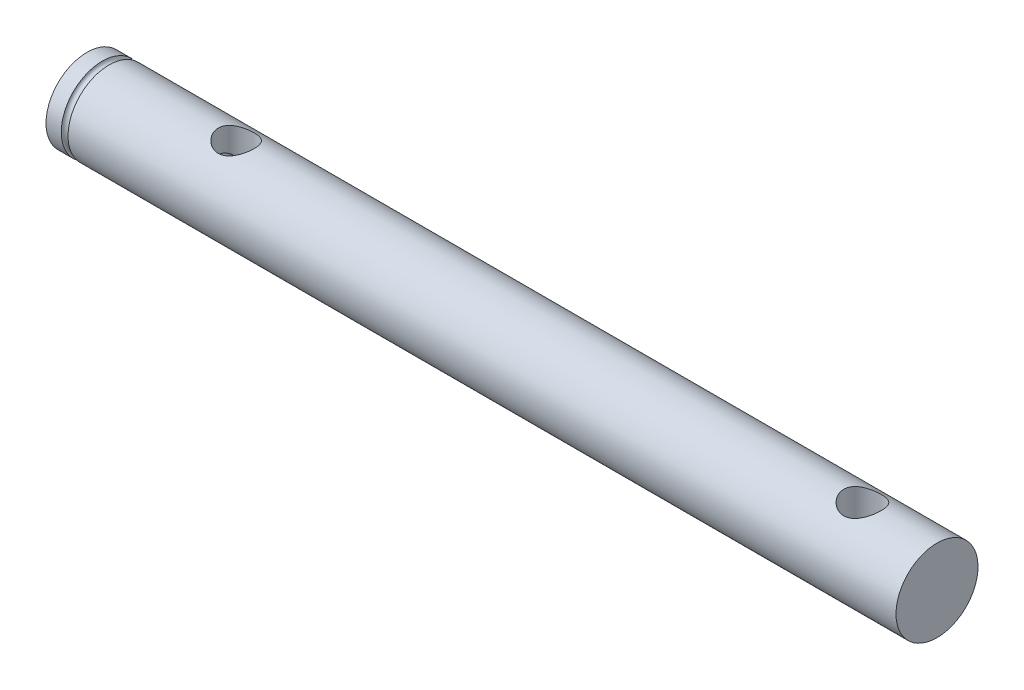
SolidWorks part; units mm, degrees
ref_plane "Plano frontal" through (0, 0, 0) normal (0, 0, 1) x (1, 0, 0)
ref_plane "Plano superior" through (0, 0, 0) normal (0, 1, 0) x (1, 0, 0)
ref_plane "Plano direito" through (0, 0, 0) normal (1, 0, 0) x (0, 0, -1)
sketch "Esboço1" plane through (0, 0, 0) normal (0, 0, 1) x (1, 0, 0)
  line L0 (40, 0) -> (228, 0)
  line L1 (228, 0) -> (228, 11)
  line L2 (228, 11) -> (5.9, 11)
  line L3 (0, 11) -> (0, 5.5)
  line L4 (0, 5.5) -> (3, 5.5)
  line L5 (3, 5.5) -> (3, 7.5)
  line L6 (3, 7.5) -> (7, 7.5)
  line L7 (7, 7.5) -> (7, 4.8)
  line L8 (7, 4.8) -> (40, 4.8)
  line L9 (40, 4.8) -> (40, 0)
  line L11 (4.1, 11) -> (0, 11)
  arc A0 (4.1, 11) -> (5.9, 11) centre (5, 11) ccw
  point P3 (228, 5.5)
  dimension "D9" = 0.9
  dimension "D1" = 3
  dimension "D2" = 4
  dimension "D3" = 33
  dimension "D4" = 11
  dimension "D5" = 7.5
  dimension "D6" = 5.5
  dimension "D7" = 4.8
  dimension "D8" = 228
  dimension "D10" = 5
revolve "Revolução1" add sketch "Esboço1" angle 360 about L0
sketch "Esboço9" plane through (0, 0, 0) normal (0, 0, 1) x (1, 0, 0)
  line L1 (7, 7.5) -> (3, 7.5)
  line L2 (7, 7.5) -> (7, -7.5)
  line L3 (7, -7.5) -> (3, -7.5)
  line L4 (3, 7.5) -> (3, -7.5)
extrude "Corte-extrusão5" cut sketch "Esboço9" against normal through all
sketch "Esboço10" plane through (0, 0, 0) normal (0, 0, 1) x (1, 0, 0)
  line L1 (0, 5.5) -> (3, 5.5)
  line L2 (0, 5.5) -> (0, -5.5)
  line L3 (0, -5.5) -> (3, -5.5)
  line L4 (3, 5.5) -> (3, -5.5)
extrude "Corte-extrusão6" cut sketch "Esboço10" against normal through all
sketch "Esboço12" plane through (0, 0, 0) normal (0, 1, 0) x (1, 0, 0)
  line L0 (40, 4.8) -> (40, -4.8) construction
  circle A0 centre (40, 0) radius 4.8
extrude "Corte-extrusão7" cut sketch "Esboço12" along normal through all and the other way blind 4.8
sketch "Esboço16" plane through (0, 0, 0) normal (0, 1, 0) x (1, 0, 0)
  line L2 (7, 0) -> (3, 0) construction
  circle A0 centre (5, 5) radius 0.9
  dimension "D1" = 5
extrude "Corte-extrusão10" cut sketch "Esboço16" against normal through all
sketch "Esboço17" plane through (0, 0, 0) normal (0, 1, 0) x (1, 0, 0)
  line L0 (0, 9.5263) -> (0, -11) construction
  circle A0 centre (208, 0) radius 5
  dimension "D1" = 208
  dimension "D2" = 10
extrude "Corte-extrusão11" cut sketch "Esboço17" against normal mid plane 22
